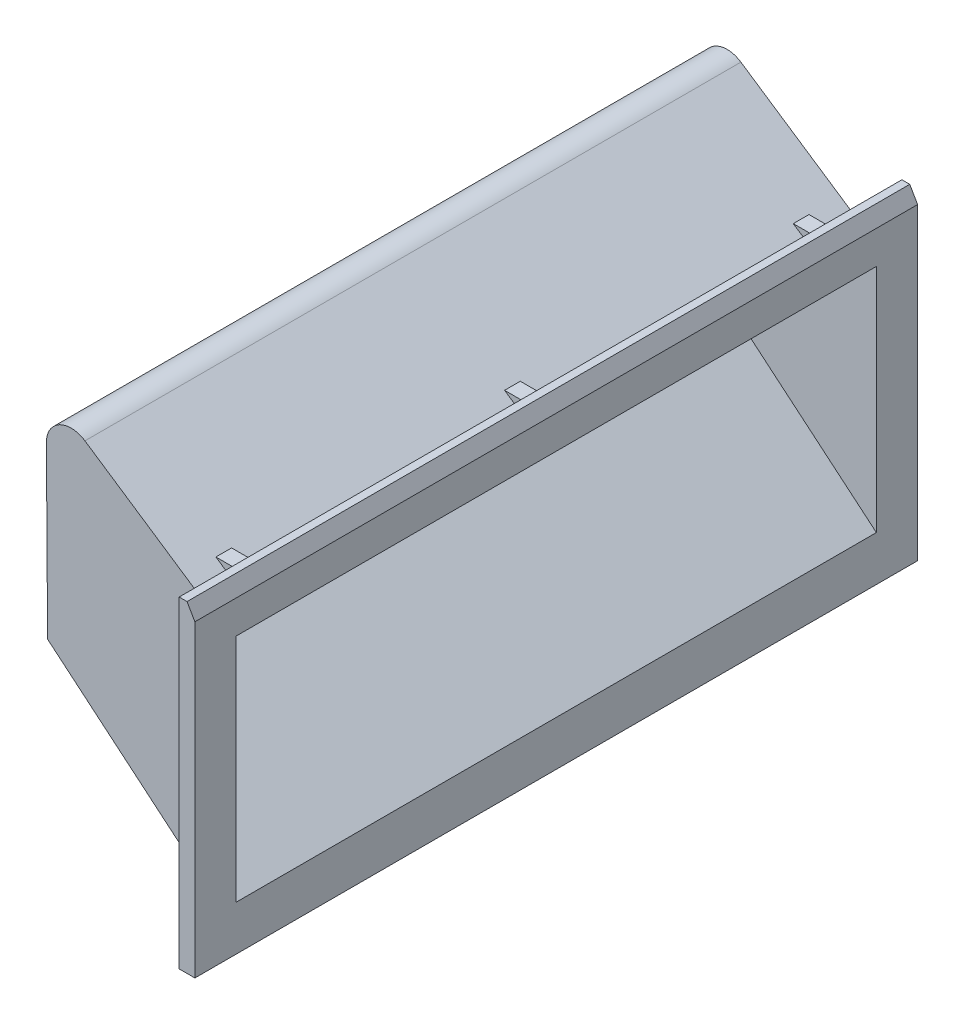
SolidWorks part; units mm, degrees
material "冷轧钢板"
ref_plane "前视基准面" through (0, 0, 0) normal (0, 0, 1) x (1, 0, 0)
ref_plane "上视基准面" through (0, 0, 0) normal (0, 1, 0) x (1, 0, 0)
ref_plane "右视基准面" through (0, 0, 0) normal (1, 0, 0) x (0, 0, -1)
sketch "草图1" plane through (0, 0, 0) normal (0, 0, 1) x (1, 0, 0)
  line L0 (-2, 41) -> (-2, 0)
  line L1 (-2, 0) -> (0, 0)
  line L2 (0, 0) -> (0, 39.2679)
  line L3 (0, 39.2679) -> (-1, 41)
  line L4 (-1, 41) -> (-2, 41)
extrude "凸台-拉伸1" add sketch "草图1" against normal blind 46 and the other way blind 46
sketch "草图2" plane through (0, 0, 0) normal (0, 0, 1) x (1, 0, 0)
  line L0 (-23.1544, 45.3229) -> (-23, 23.7239)
  line L1 (-23, 23.7239) -> (-2, 6.1028)
  line L2 (-2, 6.1028) -> (-2, 37.1075)
  line L3 (-2, 37.1075) -> (-18.2469, 47.968)
  arc A0 (-18.2469, 47.968) -> (-23.1544, 45.3229) centre (-20, 45.3455) ccw
extrude "凸台-拉伸2" add sketch "草图2" against normal blind 41.75 and the other way blind 41.75
sketch "草图3" plane through (0, 0, 0) normal (0, 0, 1) x (1, 0, 0)
  line L0 (-22, 24.1902) -> (0, 5.73)
  line L1 (0, 5.73) -> (0, 35.0715)
  line L2 (0, 35.0715) -> (-18.9193, 47.1844)
  line L3 (-21.9977, 45.5002) -> (-22, 24.1902)
  arc A0 (-18.9193, 47.1844) -> (-21.9977, 45.5002) centre (-19.9977, 45.5) ccw
extrude "切除-拉伸1" cut sketch "草图3" along normal blind 40.75 and the other way blind 40.75
ref_plane "基准面1" through (0, 0, 36.75) normal (0, 0, 1) x (1, 0, 0)
ref_plane "基准面2" through (0, 0, -36.75) normal (0, 0, 1) x (1, 0, 0)
sketch "草图4" plane through (0, 0, 0) normal (0, 0, 1) x (1, 0, 0)
  line L0 (-8.2101, 39.5) -> (-3.5, 37.3036)
  line L1 (-3.5, 37.3036) -> (-3.5, 39.5)
  line L2 (-3.5, 39.5) -> (-8.2101, 39.5)
extrude "凸台-拉伸3" add sketch "草图4" against normal blind 1 and the other way blind 1
sketch "草图5" plane through (0, 0, 36.75) normal (0, 0, 1) x (1, 0, 0)
  line L0 (-8.2101, 39.5) -> (-3.5, 37.3036)
  line L1 (-3.5, 37.3036) -> (-3.5, 39.5)
  line L2 (-3.5, 39.5) -> (-8.2101, 39.5)
sketch "草图6" plane through (0, 0, -36.75) normal (0, 0, 1) x (1, 0, 0)
  line L0 (-8.2101, 39.5) -> (-3.5, 37.3036)
  line L1 (-3.5, 37.3036) -> (-3.5, 39.5)
  line L2 (-3.5, 39.5) -> (-8.2101, 39.5)
extrude "凸台-拉伸4" add sketch "草图6" against normal blind 1 and the other way blind 1
extrude "凸台-拉伸5" add sketch "草图5" against normal blind 1 and the other way blind 1
sketch "草图7" plane through (0, 0, -36.75) normal (0, 0, 1) x (1, 0, 0)
  line L0 (-13.2017, 16.2075) -> (-3.5, 4.6455)
  line L1 (-3.5, 4.6455) -> (-3.5, 8.0669)
  line L2 (-3.5, 8.0669) -> (-13.2017, 16.2075)
extrude "凸台-拉伸6" add sketch "草图7" against normal blind 2 and the other way blind 2
sketch "草图8" plane through (0, 0, 36.75) normal (0, 0, 1) x (1, 0, 0)
  line L0 (-13.2017, 16.2075) -> (-3.5, 4.6455)
  line L1 (-3.5, 4.6455) -> (-3.5, 8.0669)
  line L2 (-3.5, 8.0669) -> (-13.2017, 16.2075)
extrude "凸台-拉伸7" add sketch "草图8" against normal blind 2 and the other way blind 2
